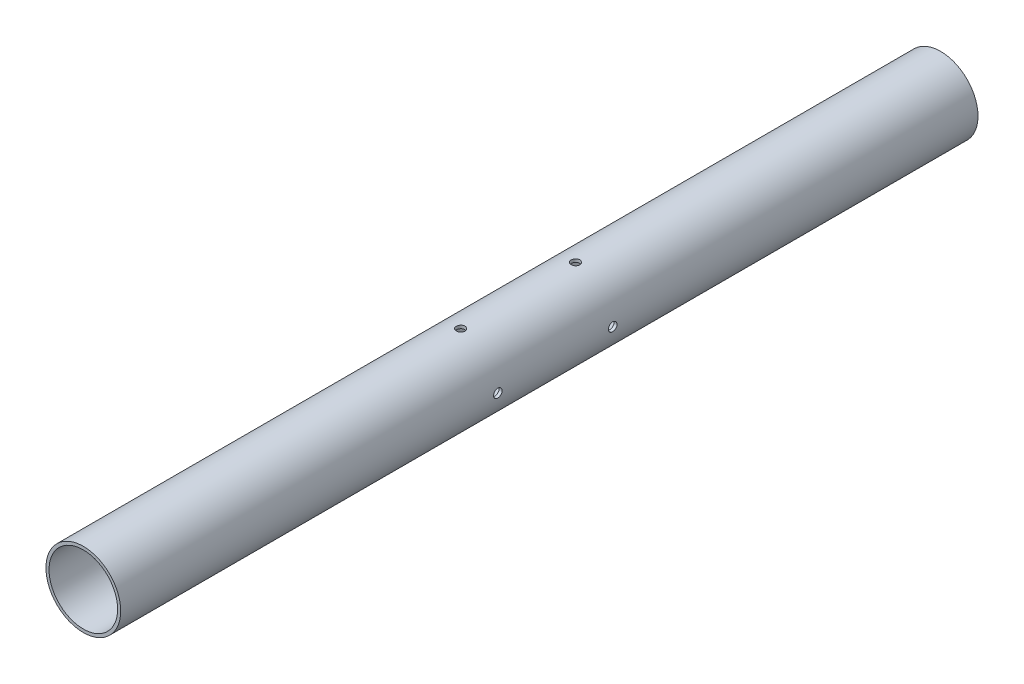
SolidWorks part; units mm, degrees
ref_plane "Front Plane" through (0, 0, 0) normal (1, 0, 0) x (0, 1, 0)
ref_plane "Top Plane" through (0, 0, 0) normal (0, 0, 1) x (0, 1, 0)
ref_plane "Right Plane" through (0, 0, 0) normal (0, 1, 0) x (-1, 0, 0)
sketch "Sketch2" plane through (0, 0, 0) normal (0, 0, 1) x (0, 1, 0)
  circle A0 centre (0, 0) radius 27.686
  circle A2 centre (0, 0) radius 25.4
  dimension "D1" = 55.372
  dimension "D2" = 50.8
extrude "tube_extrude" add sketch "Sketch2" along normal blind 635
ref_plane "bolthole_plane" through (-27.686, 0, 0) normal (-1, 0, 0) x (0, 0, 1)
sketch "Sketch4" plane through (-27.686, 0, 0) normal (-1, 0, 0) x (0, 0, 1)
  line L0 (0, 0) -> (635, 0) construction
  line L1 (635, -25.4) -> (635, 25.4) construction
  circle A0 centre (355.6, 0) radius 3.175
  circle A1 centre (270.51, 0) radius 3.175
  dimension "D1" = 6.35
  dimension "D3" = 6.35
  dimension "D2" = 279.4
  dimension "D4" = 85.09
extrude "boltholes" cut sketch "Sketch4" against normal up to next
pattern_circular "CirPattern2" count 4 over 360 about axis through (0, 0, 635) along (0, 0, -1) of "boltholes" reverse direction yes
